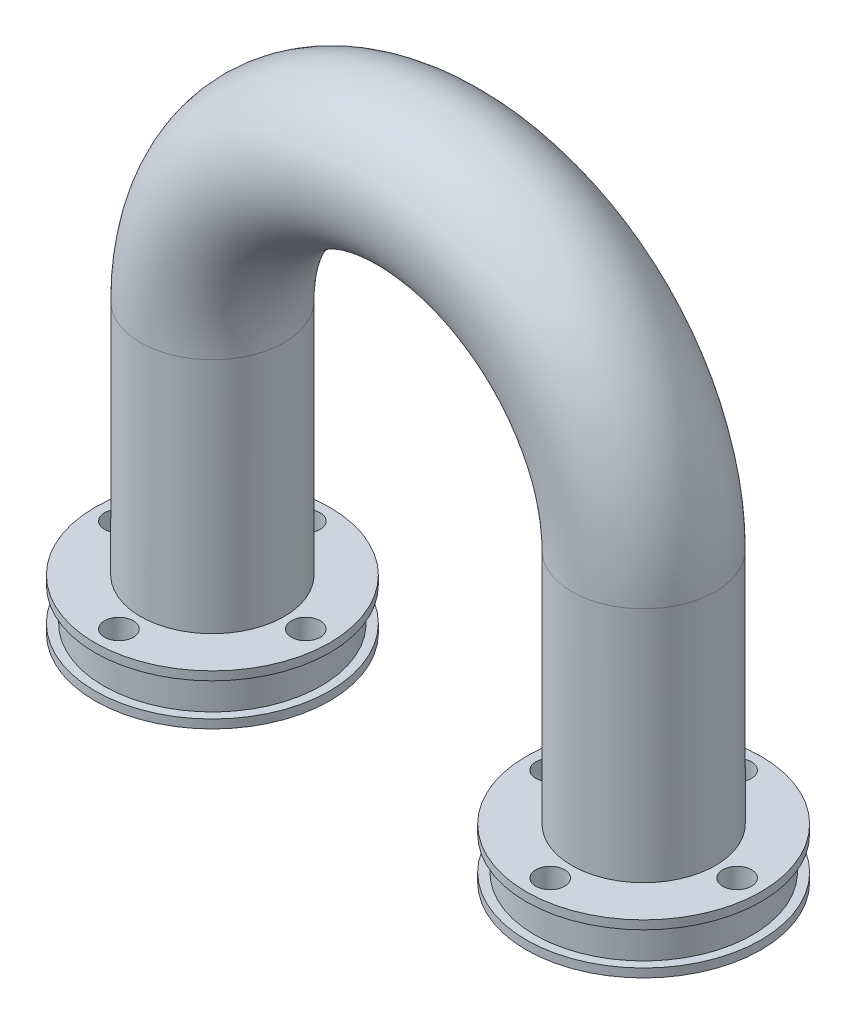
SolidWorks part; units mm, degrees
ref_plane "Front Plane" through (0, 0, 0) normal (0, 0, 1) x (1, 0, 0)
ref_plane "Top Plane" through (0, 0, 0) normal (0, 1, 0) x (1, 0, 0)
ref_plane "Right Plane" through (0, 0, 0) normal (1, 0, 0) x (0, 0, -1)
sketch "Sketch1" plane through (0, 0, 0) normal (0, 0, 1) x (1, 0, 0)
  line L0 (-30, 0) -> (-30, -33)
  line L1 (30, 0) -> (30, -33)
  arc A0 (30, 0) -> (-30, 0) centre (0, 0) ccw
  dimension "D1" = 60
  dimension "D2" = 33
ref_plane "Plane1" through (-30, -33, 0) normal (0, -1, 0) x (-1, 0, 0)
sketch "Sketch2" plane through (-30, -33, 0) normal (0, -1, 0) x (-1, 0, 0)
  line L0 (-60, 0) -> (0, 0) construction
  circle A0 centre (0, 0) radius 10
  dimension "D1" = 20
sweep "Sweep1" add profiles "Sketch2" path "Sketch1"
shell "Shell1" thickness 4 removed face at (20, -33, 0) removed face at (-20, -33, 0)
sketch "Sketch6" plane through (0, 0, 0) normal (0, 0, 1) x (1, 0, 0)
  line L0 (-48.15, -33) -> (-11.85, -33) construction
  line L1 (-36, -33) -> (-36, -40)
  line L2 (-36, 0) -> (-36, -33) construction
  line L3 (-36, -40) -> (-46.3306, -40)
  line L4 (-46.3306, -40) -> (-46.3306, -38.8)
  line L5 (-46.3306, -38.8) -> (-45.1306, -38.8)
  line L6 (-45.1306, -38.8) -> (-45.1306, -34.2)
  line L7 (-45.1306, -34.2) -> (-46.3306, -34.2)
  line L8 (-46.3306, -34.2) -> (-46.3306, -33)
  line L9 (-46.3306, -33) -> (-36, -33)
  line L10 (-30, -33) -> (-30, -26.5959) construction
  line L11 (-20, -33) -> (-20, 0) construction
  dimension "D1" = 1.2
  dimension "D2" = 1.2
  dimension "D3" = 4.6
  dimension "D4" = 1.2
  dimension "D5" = 1.2
  dimension "D6" = 10
revolve "Revolve1" add sketch "Sketch6" angle 360 about L10
sketch "Sketch8" plane through (-30, -33, 0) normal (0, -1, 0) x (-1, 0, 0)
  circle A2 centre (0, -13) radius 2
  circle A3 centre (-13, 0) radius 2
  circle A4 centre (0, 13) radius 2
  circle A5 centre (13, 0) radius 2
  point P14 (0, 0)
  dimension "D2" = 4
  dimension "D3" = 4
extrude "Cut-Extrude2" cut sketch "Sketch8" against normal mid plane 20
mirror "Mirror3" about plane through (0, 0, 0) normal (1, 0, 0) of "Revolve1", "Cut-Extrude2"
